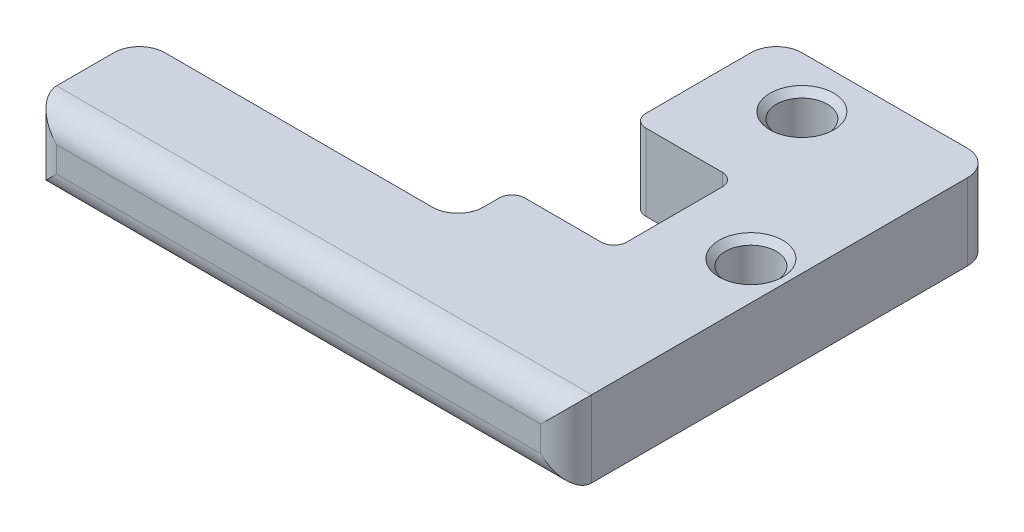
SolidWorks part; units mm, degrees
ref_plane "Front Plane" through (0, 0, 0) normal (0, 0, 1) x (1, 0, 0)
ref_plane "Top Plane" through (0, 0, 0) normal (0, 1, 0) x (1, 0, 0)
ref_plane "Right Plane" through (0, 0, 0) normal (1, 0, 0) x (0, 0, -1)
sketch "Sketch1" plane through (0, 0, 0) normal (0, 1, 0) x (1, 0, 0)
  line L1 (-8.5, 12.5) -> (8.5, 12.5)
  line L2 (-8.5, 12.5) -> (-8.5, -12.5)
  line L3 (-8.5, -12.5) -> (8.5, -12.5)
  line L4 (8.5, 12.5) -> (8.5, -12.5)
  line L5 (-8.5, 12.5) -> (8.5, -12.5) construction
  line L6 (-8.5, -12.5) -> (8.5, 12.5) construction
  line L7 (8.5, -12.5) -> (-33.5, -12.5)
  line L8 (8.5, -12.5) -> (8.5, -21)
  line L9 (8.5, -21) -> (-33.5, -21)
  line L10 (-33.5, -12.5) -> (-33.5, -21)
  point P0 (0, 0)
  dimension "D1" = 25
  dimension "D2" = 17
  dimension "D3" = 8.5
  dimension "D4" = 42
extrude "Boss-Extrude1" add sketch "Sketch1" along normal blind 6 contours L7 L10 L9 L8 L3 | L4 L1 L2 L3 region at (0, 0, 0) region at (-12.5, 0, 16.75)
sketch "Sketch2" plane through (0, 6, 0) normal (0, 1, 0) x (1, 0, 0)
  line L0 (-8.5, -12.5) -> (5.5, -12.5) construction
  line L1 (5.5, -12.5) -> (5.5, 8.5) construction
  line L2 (5.5, 8.5) -> (-2.5, 8.5) construction
  circle A0 centre (-2.5, 8.5) radius 2
  circle A1 centre (5.5, -3.5) radius 2
  dimension "D5" = 4
  dimension "D1" = 14
  dimension "D2" = 21
  dimension "D3" = 8
  dimension "D4" = 9
extrude "Cut-Extrude1" cut sketch "Sketch2" against normal through all
fillet "Fillet2" radius 2 4 edges at (-33.5, 3, 21) (-12.5, 6, 21) (8.5, 3, 21) (-12.5, 0, 21)
fillet "Fillet1" radius 2 4 edges at (-8.5, 3, 12.5) (-8.5, 3, -12.5) (8.5, 3, -12.5) (-33.5, 3, 12.5)
sketch "Sketch3" plane through (0, 6, 0) normal (0, 1, 0) x (1, 0, 0)
  circle A0 centre (-2.5, 8.5) radius 2.5
  circle A1 centre (5.5, -3.5) radius 2.5
  dimension "D1" = 5
extrude "Cut-Extrude2" cut sketch "Sketch3" against normal through all from offset 4 offset against normal yes
chamfer "Chamfer1" distance 0.5 angle 45 2 edges at (5.5, 6, 5.5) (-2.5, 6, -6.5)
fillet "Fillet3" radius 1 2 edges at (-2.5, 2, -6) (5.5, 2, 6)
sketch "Sketch4" plane through (0, 6, 0) normal (0, 1, 0) x (1, 0, 0)
  line L0 (5.5, -3.5) -> (-4.5, -3.5) construction
  line L2 (-8.5, 1.25) -> (-0.5, 1.25)
  line L3 (-8.5, 1.25) -> (-8.5, -8.25)
  line L4 (-8.5, -8.25) -> (-0.5, -8.25)
  line L5 (-0.5, 1.25) -> (-0.5, -8.25)
  line L6 (-8.5, 1.25) -> (-0.5, -8.25) construction
  line L7 (-8.5, -8.25) -> (-0.5, 1.25) construction
  dimension "D1" = 10
  dimension "D2" = 8
  dimension "D3" = 9.5
extrude "Cut-Extrude3" cut sketch "Sketch4" against normal through all
fillet "Fillet4" radius 1 4 edges at (-0.5, 3, 8.25) (-0.5, 3, -1.25) (-8.5, 3, 8.25) (-8.5, 3, -1.25)
